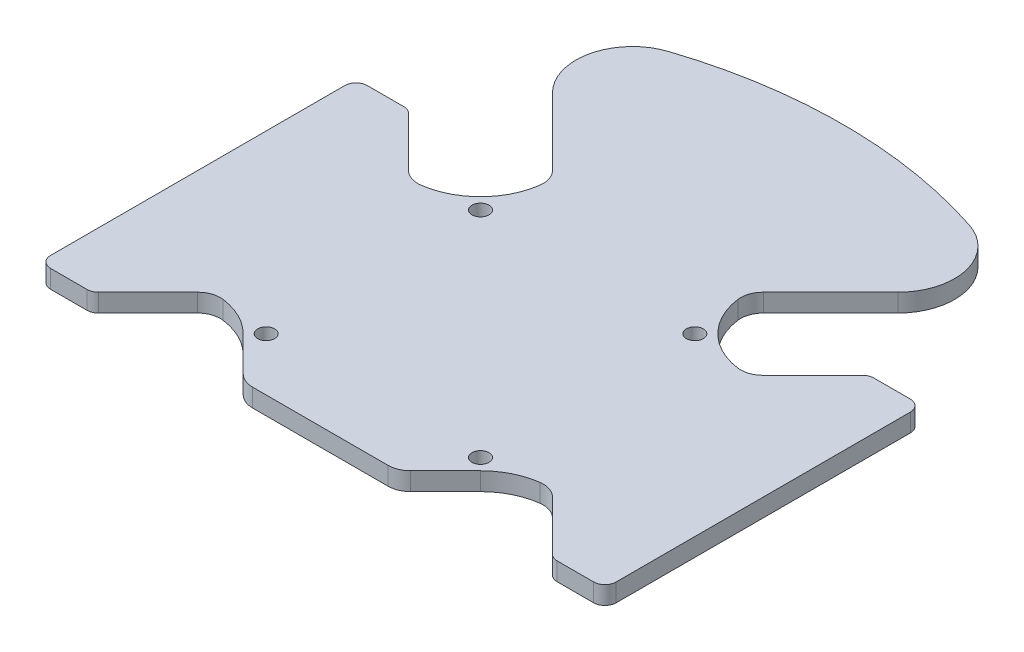
SolidWorks part; units mm, degrees
ref_plane "Front Plane" through (0, 0, 0) normal (0, 0, 1) x (1, 0, 0)
ref_plane "Top Plane" through (0, 0, 0) normal (0, 1, 0) x (1, 0, 0)
ref_plane "Right Plane" through (0, 0, 0) normal (1, 0, 0) x (0, 0, -1)
sketch "Sketch1" plane through (0, 0, 0) normal (0, 1, 0) x (1, 0, 0)
  line L1 (-25, 14) -> (25, 14) construction
  line L2 (-25, 14) -> (-25, -14) construction
  line L3 (-25, -14) -> (25, -14) construction
  line L4 (25, 14) -> (25, -14) construction
  line L16 (-20.0711, -13.7071) -> (-15.6818, -9.3178)
  line L17 (20.0711, -13.7071) -> (15.6818, -9.3178)
  line L20 (-20.7782, -14) -> (-24, -14)
  line L21 (-25, -13) -> (-25, 13)
  line L22 (-24, 14) -> (-20.7782, 14)
  line L23 (-20.0711, 13.7071) -> (-15.6818, 9.3178)
  line L25 (20.7782, -14) -> (24, -14)
  line L26 (25, -13) -> (25, 13)
  line L27 (24, 14) -> (20.7782, 14)
  line L28 (20.0711, 13.7071) -> (15.6818, 9.3178)
  line L29 (-10.4887, 10.4887) -> (0, 0) construction
  line L30 (0, 0) -> (10.4887, 10.4887) construction
  line L31 (9.3178, 15.6818) -> (15.2748, 21.6388)
  line L35 (-15.2748, 21.6388) -> (-9.3178, 15.6818)
  line L36 (-5.9885, -14.1605) -> (5.9885, -14.1605)
  line L38 (0, 0) -> (-10.4887, -10.4887) construction
  line L39 (10.4887, -10.4887) -> (0, 0) construction
  line L40 (-10.4887, -10.4887) -> (-7.4027, -13.5748)
  line L41 (7.4027, -13.5748) -> (10.4887, -10.4887)
  arc A2 (-14, 8.75) -> (-8.75, 14) centre (-14.8193, 14.8193) ccw
  arc A3 (14, 8.75) -> (8.75, 14) centre (14.8193, 14.8193) cw
  arc A4 (-15.6818, 9.3178) -> (-14, 8.75) centre (-14.2676, 10.732) ccw
  arc A5 (14, 8.75) -> (15.6818, 9.3178) centre (14.2676, 10.732) ccw
  arc A8 (8.75, 14) -> (9.3178, 15.6818) centre (10.732, 14.2676) cw
  arc A9 (-8.75, 14) -> (-9.3178, 15.6818) centre (-10.732, 14.2676) ccw
  arc A12 (15.2748, 21.6388) -> (13.3004, 29.9244) centre (11.7393, 25.1743) ccw
  arc A13 (-13.3004, 29.9244) -> (-15.2748, 21.6388) centre (-11.7393, 25.1743) ccw
  arc A14 (25, 13) -> (24, 14) centre (24, 13) ccw
  arc A15 (24, -14) -> (25, -13) centre (24, -13) ccw
  arc A17 (20.7782, 14) -> (20.0711, 13.7071) centre (20.7782, 13) ccw
  arc A18 (-20.7782, 14) -> (-20.0711, 13.7071) centre (-20.7782, 13) cw
  arc A19 (-25, 13) -> (-24, 14) centre (-24, 13) cw
  arc A20 (-24, -14) -> (-25, -13) centre (-24, -13) cw
  arc A22 (-13.3004, 29.9244) -> (13.3004, 29.9244) centre (0, -10.5462) cw
  arc A23 (-15.6818, -9.3178) -> (-14, -8.75) centre (-14.2676, -10.732) cw
  arc A24 (-14, -8.75) -> (-10.4887, -10.4887) centre (-14.8193, -14.8193) cw
  arc A25 (15.6818, -9.3178) -> (14, -8.75) centre (14.2676, -10.732) ccw
  arc A26 (14, -8.75) -> (10.4887, -10.4887) centre (14.8193, -14.8193) ccw
  arc A29 (5.9885, -14.1605) -> (7.4027, -13.5748) centre (5.9885, -12.1605) ccw
  arc A30 (-5.9885, -14.1605) -> (-7.4027, -13.5748) centre (-5.9885, -12.1605) cw
  arc A31 (20.7782, -14) -> (20.0711, -13.7071) centre (20.7782, -13) cw
  arc A32 (-20.7782, -14) -> (-20.0711, -13.7071) centre (-20.7782, -13) ccw
  circle A33 centre (-9.4752, 9.4752) radius 0.75
  circle A34 centre (9.4752, -9.4752) radius 0.75
  circle A35 centre (9.4752, 9.4752) radius 0.75
  circle A36 centre (-9.4752, -9.4752) radius 0.75
  point P4 (0, 14)
  point P6 (-25, 0)
  point P7 (0, -14.1605)
  point P29 (0, 0)
  point P31 (3.1528, -16.9963)
  point P39 (5.9885, -14.1605)
  point P48 (22.3928, 28.9689)
  point P51 (0, 0)
  point P58 (-22.3928, 28.9689)
  point P70 (20.364, 14)
  point P73 (-20.364, 14)
  point P88 (0, 0)
  point P89 (-4.5688, -15.5803)
  point P90 (0, 0)
  dimension "D9" = 2
  dimension "D10" = 2
  dimension "D11" = 2
  dimension "D12" = 1
  dimension "D13" = 5
  dimension "D14" = 1
  dimension "D15" = 1.5
  dimension "D1" = 50
  dimension "D2" = 28
  dimension "D3" = 9
  dimension "D4" = 9
  dimension "D5" = 45
  dimension "D6" = 45
  dimension "D7" = 17.5
  dimension "D16" = 26.8
extrude "Boss-Extrude1" add sketch "Sketch1" along normal blind 1.6
ref_axis "Axis1" through (0, 1.68, 0) along (0, -1, 0)
